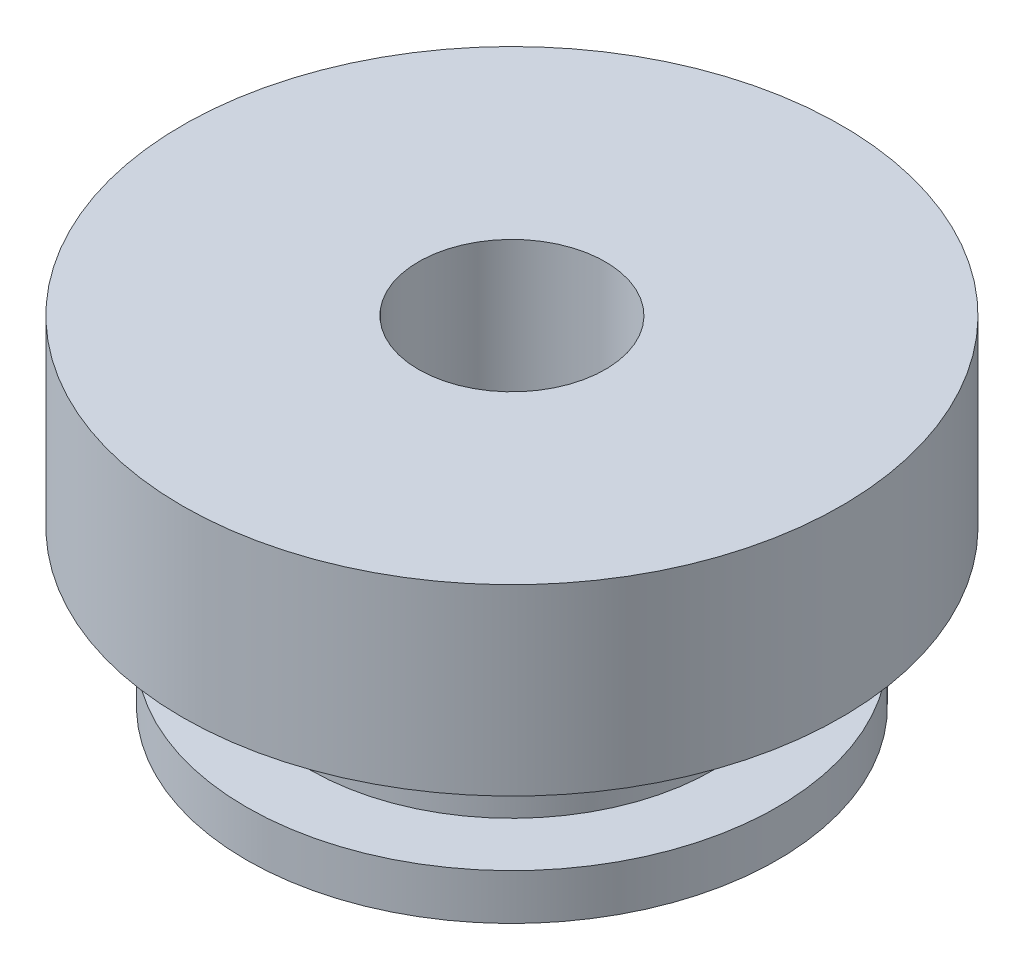
SolidWorks part; units mm, degrees
ref_plane "Front Plane" through (0, 0, 0) normal (0, 0, 1) x (1, 0, 0)
ref_plane "Top Plane" through (0, 0, 0) normal (0, 1, 0) x (1, 0, 0)
ref_plane "Right Plane" through (0, 0, 0) normal (1, 0, 0) x (0, 0, -1)
sketch "Sketch1" plane through (0, 0, 0) normal (0, 1, 0) x (1, 0, 0)
  circle A0 centre (0, 0) radius 7.25
  dimension "D1" = 14.5
extrude "Boss-Extrude1" add sketch "Sketch1" along normal blind 1.25
sketch "Sketch2" plane through (0, 1.25, 0) normal (0, 1, 0) x (1, 0, 0)
  circle A0 centre (0, 0) radius 5.5
  dimension "D1" = 11
extrude "Boss-Extrude2" add sketch "Sketch2" along normal blind 3
sketch "Sketch3" plane through (0, 4.25, 0) normal (0, 1, 0) x (1, 0, 0)
  circle A0 centre (0, 0) radius 9
  dimension "D1" = 18
extrude "Boss-Extrude3" add sketch "Sketch3" along normal blind 5
sketch "Sketch4" plane through (0, 9.25, 0) normal (0, 1, 0) x (1, 0, 0)
  circle A0 centre (0, 0) radius 2.55
  dimension "D1" = 5.1
extrude "Cut-Extrude1" cut sketch "Sketch4" against normal up to surface (8 mm away) up to face at (0, 1.25, 7.25)
